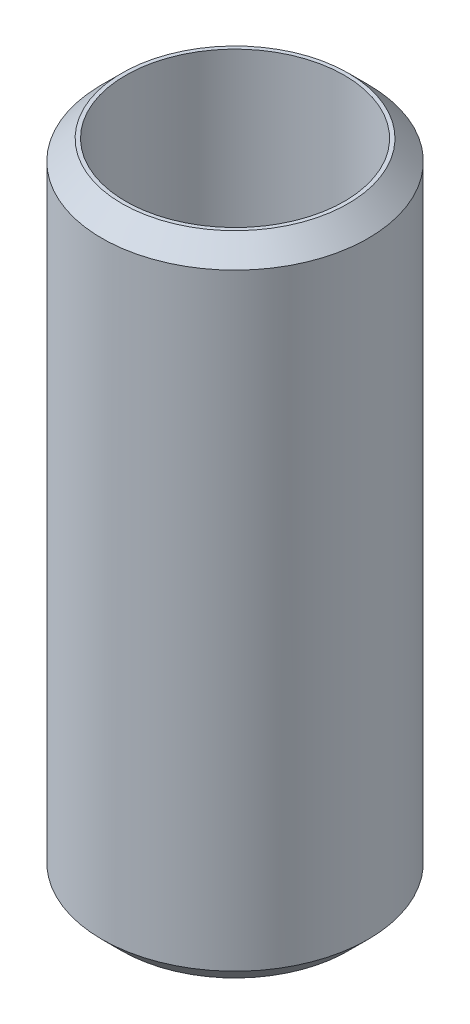
SolidWorks part; units mm, degrees
ref_plane "Front Plane" through (0, 0, 0) normal (0, 0, 1) x (1, 0, 0)
ref_plane "Top Plane" through (0, 0, 0) normal (0, 1, 0) x (1, 0, 0)
ref_plane "Right Plane" through (0, 0, 0) normal (1, 0, 0) x (0, 0, -1)
sketch "Sketch1" plane through (0, 0, 0) normal (0, 1, 0) x (1, 0, 0)
  circle A0 centre (0, 0) radius 30
  dimension "SHAFT_OD" = 60
extrude "Boss-Extrude1" add sketch "Sketch1" along normal blind 145.8251
sketch "Sketch2" plane through (0, 0, 0) normal (0, 1, 0) x (1, 0, 0)
  circle A0 centre (0, 0) radius 24.626
  dimension "BORE_D" = 49.252
extrude "Cut-Extrude1" cut sketch "Sketch2" along normal through all
chamfer "Chamfer1" distance 4.5133 angle 45 2 edges at (0, 145.8251, 30) (0, 0, 30)
